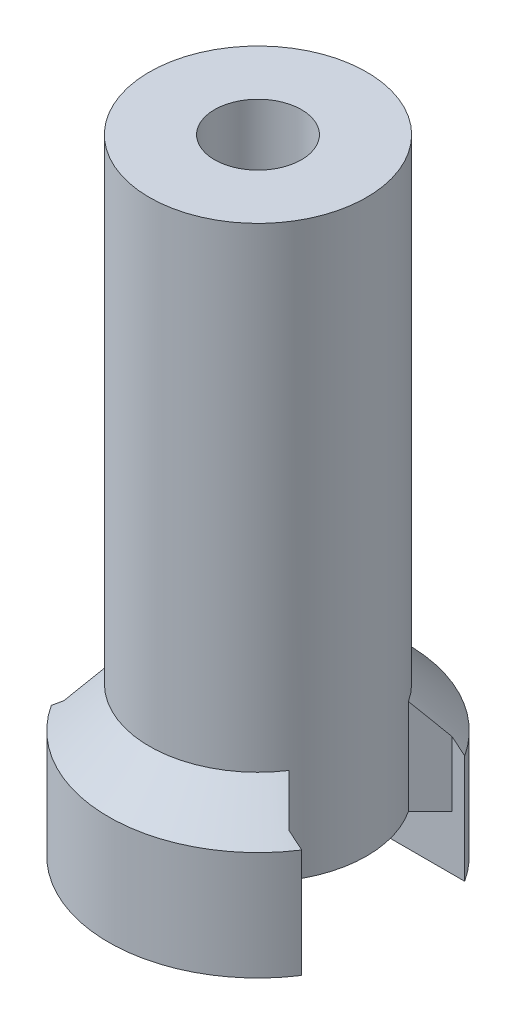
SolidWorks part; units mm, degrees
ref_plane "Front Plane" through (0, 0, 0) normal (0, 0, 1) x (1, 0, 0)
ref_plane "Top Plane" through (0, 0, 0) normal (0, 1, 0) x (1, 0, 0)
ref_plane "Right Plane" through (0, 0, 0) normal (1, 0, 0) x (0, 0, -1)
sketch "Sketch1" plane through (0, 0, 0) normal (0, 1, 0) x (1, 0, 0)
  circle A0 centre (0, 0) radius 4
  circle A1 centre (0, 0) radius 1.6
  dimension "D1" = 8
  dimension "D2" = 3.2
extrude "Boss-Extrude1" add sketch "Sketch1" along normal blind 23
sketch "Sketch3" plane through (0, 0, 0) normal (0, -1, 0) x (1, 0, 0)
  line L0 (-6.778, -3) -> (6.778, 3) construction
  line L1 (-6.778, 3) -> (6.778, 3)
  line L2 (-6.778, 3) -> (-6.778, -3)
  line L3 (-6.778, -3) -> (6.778, -3)
  line L4 (6.778, 3) -> (6.778, -3)
  circle A0 centre (0, 0) radius 1.6
  point P7 (0, 0)
  dimension "D1" = 6
extrude "Cut-Extrude1" cut sketch "Sketch3" against normal blind 2
sketch "Sketch5" plane through (0, 0, 0) normal (0, -1, 0) x (1, 0, 0)
  line L0 (-4.6098, 3) -> (4.6098, 3)
  line L1 (4.6098, -3) -> (-4.6098, -3)
  line L2 (2.6458, 3) -> (-2.6458, 3) construction
  arc A0 (-4.6098, -3) -> (4.6098, -3) centre (0, 0) ccw
  arc A1 (-2.6458, -3) -> (2.6458, -3) centre (0, 0) ccw construction
  arc A3 (4.6098, 3) -> (-4.6098, 3) centre (0, 0) ccw
  dimension "D1" = 1.5
extrude "Boss-Extrude2" add sketch "Sketch5" against normal blind 4
chamfer "Chamfer1" distance 1.5 angle 45 6 edges at (2.6458, 3, -3) (-2.6458, 3, -3) (2.6458, 3, 3) (-2.6458, 3, 3) (0, 4, 4) (0, 4, -4)
